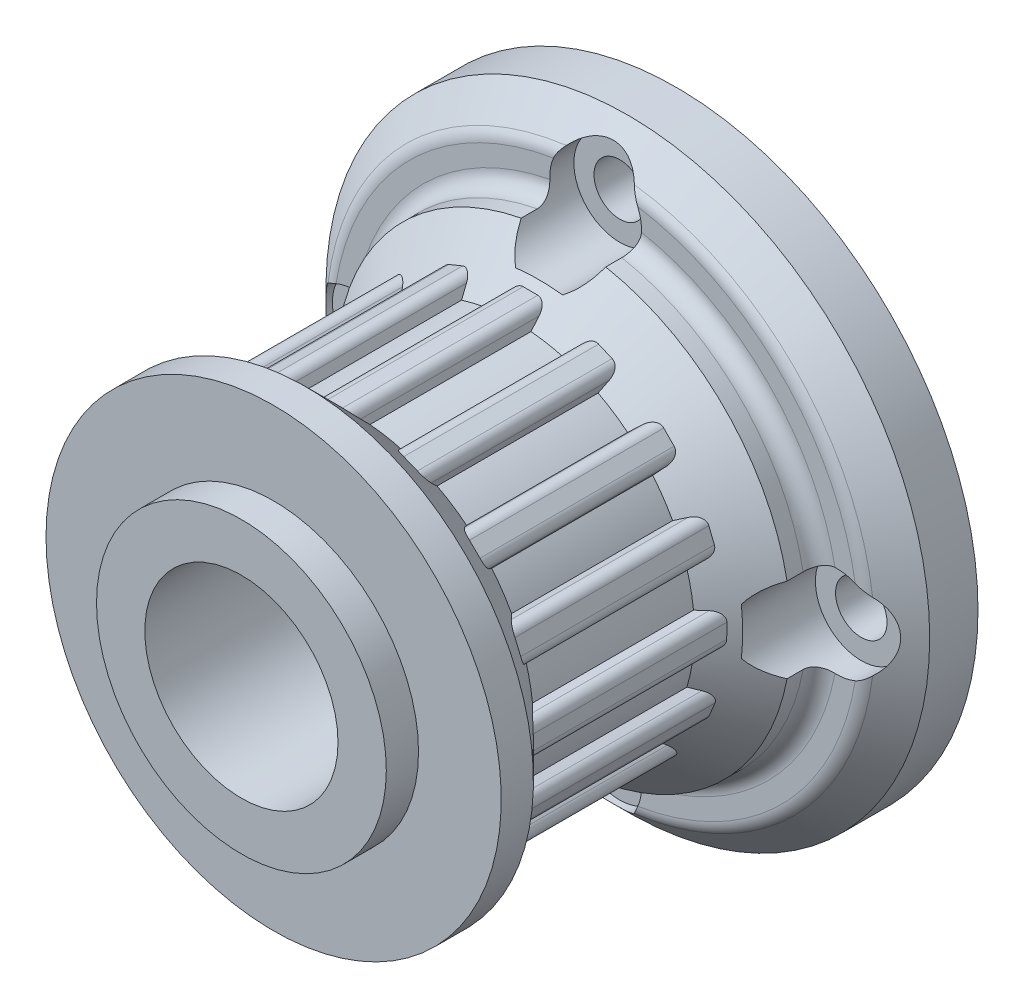
SolidWorks part; units mm, degrees
material "ABS"
ref_plane "Plan de face" through (0, 0, 0) normal (0, 0, 1) x (1, 0, 0)
ref_plane "Plan de dessus" through (0, 0, 0) normal (0, 1, 0) x (1, 0, 0)
ref_plane "Plan de droite" through (0, 0, 0) normal (1, 0, 0) x (0, 0, -1)
sketch "Esquisse5" plane through (0, 0, 0) normal (0, 0, 1) x (1, 0, 0)
  line L0 (0, 0) -> (0, 12.73) construction
  line L1 (0, 0) -> (4.8716, 11.761) construction
  line L2 (0, 12.1967) -> (0.3458, 12.1967)
  line L3 (0.9441, 11.6417) -> (0.9973, 10.9349)
  line L4 (0.9973, 10.9349) -> (3.0608, 10.5451)
  line L5 (3.0608, 10.5451) -> (3.3634, 11.174)
  line L6 (4.1337, 11.4681) -> (4.6599, 11.2501)
  line L7 (0, 0) -> (2.029, 10.74) construction
  line L8 (4.6599, 11.2501) -> (4.9794, 11.1178)
  line L9 (5.3198, 10.3761) -> (5.0985, 9.7028)
  line L10 (5.0985, 9.7028) -> (6.8557, 8.553)
  line L11 (6.8557, 8.553) -> (7.3759, 9.0181)
  line L12 (8.2001, 8.9951) -> (8.6029, 8.5923)
  line L13 (8.6029, 8.5923) -> (8.8475, 8.3478)
  line L14 (8.8781, 7.5323) -> (8.4159, 6.995)
  line L15 (8.4159, 6.995) -> (9.5994, 5.2602)
  line L16 (9.5994, 5.2602) -> (10.2581, 5.4909)
  line L17 (11.0107, 5.1542) -> (11.2287, 4.6279)
  line L18 (11.2287, 4.6279) -> (11.361, 4.3084)
  line L19 (11.0772, 3.5433) -> (10.4447, 3.2237)
  line L20 (10.4447, 3.2237) -> (10.8742, 1.1681)
  line L21 (10.8742, 1.1681) -> (11.571, 1.1292)
  line L22 (12.1375, 0.5301) -> (12.1375, -0.0395)
  line L23 (12.1375, -0.0395) -> (12.1375, -0.3853)
  line L24 (11.5825, -0.9837) -> (10.8758, -1.0368)
  line L25 (10.8758, -1.0368) -> (10.4859, -3.1003)
  line L26 (10.4859, -3.1003) -> (11.1148, -3.4029)
  line L27 (11.4089, -4.1732) -> (11.1909, -4.6995)
  line L28 (11.1909, -4.6995) -> (11.0586, -5.019)
  line L29 (10.3169, -5.3593) -> (9.6436, -5.138)
  line L30 (9.6436, -5.138) -> (8.4938, -6.8952)
  line L31 (8.4938, -6.8952) -> (8.9589, -7.4155)
  line L32 (8.9359, -8.2397) -> (8.5331, -8.6425)
  line L33 (8.5331, -8.6425) -> (8.2886, -8.887)
  line L34 (7.4731, -8.9176) -> (6.9358, -8.4555)
  line L35 (6.9358, -8.4555) -> (5.201, -9.6389)
  line L36 (5.201, -9.6389) -> (5.4317, -10.2976)
  line L37 (5.095, -11.0503) -> (4.5687, -11.2682)
  line L38 (4.5687, -11.2682) -> (4.2493, -11.4006)
  line L39 (3.4841, -11.1168) -> (3.1645, -10.4842)
  line L40 (3.1645, -10.4842) -> (1.1089, -10.9137)
  line L41 (1.1089, -10.9137) -> (1.07, -11.6105)
  line L42 (0.4709, -12.177) -> (-0.0987, -12.177)
  line L43 (-0.0987, -12.177) -> (-0.4445, -12.177)
  line L44 (-1.0428, -11.622) -> (-1.096, -10.9153)
  line L45 (-1.096, -10.9153) -> (-3.1595, -10.5255)
  line L46 (-3.1595, -10.5255) -> (-3.4621, -11.1543)
  line L47 (-4.2324, -11.4485) -> (-4.7587, -11.2305)
  line L48 (-4.7587, -11.2305) -> (-5.0781, -11.0981)
  line L49 (-5.4185, -10.3564) -> (-5.1972, -9.6831)
  line L50 (-5.1972, -9.6831) -> (-6.9544, -8.5333)
  line L51 (-6.9544, -8.5333) -> (-7.4747, -8.9985)
  line L52 (-8.2989, -8.9755) -> (-8.7017, -8.5727)
  line L53 (-8.7017, -8.5727) -> (-8.9462, -8.3282)
  line L54 (-8.9768, -7.5127) -> (-8.5147, -6.9753)
  line L55 (-8.5147, -6.9753) -> (-9.6981, -5.2406)
  line L56 (-9.6981, -5.2406) -> (-10.3568, -5.4712)
  line L57 (-11.1094, -5.1346) -> (-11.3274, -4.6083)
  line L58 (-11.3274, -4.6083) -> (-11.4598, -4.2888)
  line L59 (-11.176, -3.5237) -> (-10.5434, -3.2041)
  line L60 (-10.5434, -3.2041) -> (-10.9729, -1.1485)
  line L61 (-10.9729, -1.1485) -> (-11.6697, -1.1095)
  line L62 (-12.2362, -0.5105) -> (-12.2362, 0.0592)
  line L63 (-12.2362, 0.0592) -> (-12.2362, 0.405)
  line L64 (-11.6812, 1.0033) -> (-10.9745, 1.0565)
  line L65 (-10.9745, 1.0565) -> (-10.5846, 3.1199)
  line L66 (-10.5846, 3.1199) -> (-11.2135, 3.4226)
  line L67 (-11.5076, 4.1928) -> (-11.2897, 4.7191)
  line L68 (-11.2897, 4.7191) -> (-11.1573, 5.0386)
  line L69 (-10.4156, 5.379) -> (-9.7423, 5.1576)
  line L70 (-9.7423, 5.1576) -> (-8.5925, 6.9149)
  line L71 (-8.5925, 6.9149) -> (-9.0577, 7.4351)
  line L72 (-9.0347, 8.2593) -> (-8.6319, 8.6621)
  line L73 (-8.6319, 8.6621) -> (-8.3873, 8.9066)
  line L74 (-7.5718, 8.9373) -> (-7.0345, 8.4751)
  line L75 (-7.0345, 8.4751) -> (-5.2997, 9.6586)
  line L76 (-5.2997, 9.6586) -> (-5.5304, 10.3172)
  line L77 (-5.1938, 11.0699) -> (-4.6675, 11.2879)
  line L78 (-4.6675, 11.2879) -> (-4.348, 11.4202)
  line L79 (-3.5828, 11.1364) -> (-3.2633, 10.5038)
  line L80 (-3.2633, 10.5038) -> (-1.2077, 10.9333)
  line L81 (-1.2077, 10.9333) -> (-1.1687, 11.6301)
  line L82 (-0.5697, 12.1967) -> (0, 12.1967)
  circle A0 centre (0, 0) radius 12.73 construction
  circle A1 centre (0, 0) radius 12.23 construction
  circle A2 centre (0, 0) radius 10.93 construction
  arc A3 (4.1337, 11.4681) -> (3.3634, 11.174) centre (3.904, 10.9138) ccw
  arc A4 (0.9441, 11.6417) -> (0.3458, 12.1967) centre (0.3458, 11.5967) ccw
  arc A5 (8.2001, 8.9951) -> (7.3759, 9.0181) centre (7.7759, 8.5709) ccw
  arc A6 (5.3198, 10.3761) -> (4.9794, 11.1178) centre (4.7498, 10.5634) ccw
  arc A7 (11.0107, 5.1542) -> (10.2581, 5.4909) centre (10.4564, 4.9246) ccw
  arc A8 (8.8781, 7.5323) -> (8.8475, 8.3478) centre (8.4232, 7.9235) ccw
  arc A9 (12.1375, 0.5301) -> (11.571, 1.1292) centre (11.5375, 0.5301) ccw
  arc A10 (11.0772, 3.5433) -> (11.361, 4.3084) centre (10.8067, 4.0788) ccw
  arc A11 (11.4089, -4.1732) -> (11.1148, -3.4029) centre (10.8546, -3.9436) ccw
  arc A12 (11.5825, -0.9837) -> (12.1375, -0.3853) centre (11.5375, -0.3853) ccw
  arc A13 (8.9359, -8.2397) -> (8.9589, -7.4155) centre (8.5117, -7.8154) ccw
  arc A14 (10.3169, -5.3593) -> (11.0586, -5.019) centre (10.5043, -4.7894) ccw
  arc A15 (5.095, -11.0503) -> (5.4317, -10.2976) centre (4.8654, -10.4959) ccw
  arc A16 (7.4731, -8.9176) -> (8.2886, -8.887) centre (7.8644, -8.4627) ccw
  arc A17 (0.4709, -12.177) -> (1.07, -11.6105) centre (0.4709, -11.577) ccw
  arc A18 (3.4841, -11.1168) -> (4.2493, -11.4006) centre (4.0196, -10.8463) ccw
  arc A19 (-4.2324, -11.4485) -> (-3.4621, -11.1543) centre (-4.0028, -10.8941) ccw
  arc A20 (-1.0428, -11.622) -> (-0.4445, -12.177) centre (-0.4445, -11.577) ccw
  arc A21 (-8.2989, -8.9755) -> (-7.4747, -8.9985) centre (-7.8746, -8.5512) ccw
  arc A22 (-5.4185, -10.3564) -> (-5.0781, -11.0981) centre (-4.8485, -10.5438) ccw
  arc A23 (-11.1094, -5.1346) -> (-10.3568, -5.4712) centre (-10.5551, -4.905) ccw
  arc A24 (-8.9768, -7.5127) -> (-8.9462, -8.3282) centre (-8.5219, -7.9039) ccw
  arc A25 (-12.2362, -0.5105) -> (-11.6697, -1.1095) centre (-11.6362, -0.5105) ccw
  arc A26 (-11.176, -3.5237) -> (-11.4598, -4.2888) centre (-10.9054, -4.0592) ccw
  arc A27 (-11.5076, 4.1928) -> (-11.2135, 3.4226) centre (-10.9533, 3.9632) ccw
  arc A28 (-11.6812, 1.0033) -> (-12.2362, 0.405) centre (-11.6362, 0.405) ccw
  arc A29 (-9.0347, 8.2593) -> (-9.0577, 7.4351) centre (-8.6104, 7.8351) ccw
  arc A30 (-10.4156, 5.379) -> (-11.1573, 5.0386) centre (-10.603, 4.809) ccw
  arc A31 (-5.1938, 11.0699) -> (-5.5304, 10.3172) centre (-4.9641, 10.5156) ccw
  arc A32 (-7.5718, 8.9373) -> (-8.3873, 8.9066) centre (-7.9631, 8.4824) ccw
  arc A33 (-0.5697, 12.1967) -> (-1.1687, 11.6301) centre (-0.5697, 11.5967) ccw
  arc A34 (-3.5828, 11.1364) -> (-4.348, 11.4202) centre (-4.1184, 10.8659) ccw
  circle A36 centre (0, 0) radius 6
  point P15 (3.6094, 11.6852)
  point P19 (0.9024, 12.1967)
  point P172 (-0.0494, 0.0098)
  dimension "D1" = 25.46
  dimension "D8" = 0.6
  dimension "D10" = 12
  dimension "D2" = 22.5
  dimension "D3" = 0.5
  dimension "D4" = 1.3
  dimension "D5" = 15
  dimension "D6" = 15
  dimension "D7" = 2.1
  dimension "D9" = 16
sketch "Esquisse11" plane through (0, 0, 0) normal (0, 0, 1) x (1, 0, 0)
  line L0 (0, 15) -> (0, 0) construction
  line L1 (15, 0) -> (0, 0) construction
  line L2 (0, 0) -> (-15, 0) construction
  line L3 (0, 0) -> (0, -15) construction
  circle A1 centre (0, 0) radius 15 construction
  circle A2 centre (0, 0) radius 18.75
  circle A6 centre (-15, 0) radius 1.6
  circle A7 centre (0, 15) radius 1.6
  circle A8 centre (15, 0) radius 1.6
  circle A9 centre (0, -15) radius 1.6
  dimension "D2" = 3.2
  dimension "D3" = 3.2
  dimension "D4" = 3.2
  dimension "D5" = 3.2
  dimension "D6" = 30
  dimension "D1" = 37.5
extrude "Boss.-Extru.4" add sketch "Esquisse11" along normal blind 5
extrude "Boss.-Extru.5" add sketch "Esquisse5" along normal blind 24
sketch "Esquisse12" plane through (0, 0, 5) normal (0, 0, 1) x (1, 0, 0)
  circle A0 centre (0, 0) radius 1.6
  dimension "D1" = 3.2
extrude "Enlèv. mat.-Extru.7" cut sketch "Esquisse12" against normal blind 32
sketch "Esquisse13" plane through (0, 0, 0) normal (0, 1, 0) x (1, 0, 0)
  line L0 (0, 0) -> (0, -25.2892) construction
  line L1 (18.75, 0) -> (-18.75, 0) construction
  line L2 (6, -5) -> (6, -25)
  line L3 (6, -25) -> (14.1375, -25)
  line L4 (14.1375, -25) -> (14.1375, -23)
  line L5 (14.1375, -23) -> (11.1375, -20)
  line L6 (11.1375, -20) -> (11.1375, -10)
  line L7 (11.1375, -10) -> (14.1375, -7)
  line L8 (14.1375, -7) -> (14.1375, -5)
  line L9 (14.1375, -5) -> (6, -5)
  line L10 (12.1375, -24) -> (12.1375, -5) construction
  dimension "D1" = 6
  dimension "D2" = 2
  dimension "D3" = 2
  dimension "D4" = 45
  dimension "D5" = 45
  dimension "D6" = 10
  dimension "D8" = 5
  dimension "D9" = 2
  dimension "D10" = 20
revolve "Révolution1" add sketch "Esquisse13" angle 360 about L0
sketch "Esquisse15" plane through (0, 0, 5) normal (0, 0, 1) x (1, 0, 0)
  circle A8 centre (15, 0) radius 2.85
  circle A9 centre (0, 15) radius 2.85
  circle A10 centre (0, -15) radius 2.85
  circle A11 centre (-15, 0) radius 2.85
extrude "Enlèv. mat.-Extru.9" cut sketch "Esquisse15" against normal blind 1.5 and the other way blind 3.5
chamfer "Chanfrein1" distance 2 angle 45 1 edges at (18.75, 0, 5)
fillet "Congé1" radius 1 8 edges at (9.9967, 9.9967, 5) (-9.9967, 9.9967, 5) (-9.9967, -9.9967, 5) (9.9967, -9.9967, 5) (11.844, 11.844, 5) (11.844, -11.844, 5) (-11.844, -11.844, 5) (-11.844, 11.844, 5)
sketch "Esquisse16" plane through (0, 0, 25) normal (0, 0, 1) x (1, 0, 0)
  circle A0 centre (0, 0) radius 6 construction
  circle A1 centre (0, 0) radius 6
  circle A2 centre (0, 0) radius 9
  dimension "D1" = 18
extrude "Boss.-Extru.6" add sketch "Esquisse16" along normal blind 2
equation "\"A\"= 26"
equation "\"E\"= 20.5"
equation "\"C\"= 6"
equation "\"B\"= 16.5"
equation "\"Dp\"= 25.46'Diamètre primitif"
equation "\"Df\"= 28'Diamètre extérieur"
equation "\"Teeth\"= 16'Nombre de dents"
equation "\"L\"= 15'Largeur courroie"
equation "\"D1\" = \"A\" - \"E\" - 2"
equation "\"D1@Esquisse3\"=\"L\"+2"
equation "\"D2@Esquisse3\"=\"Dp\"/2-5"
equation "\"D1@Esquisse5\"=\"Dp\""
equation "\"D2@Esquisse5\"=360/\"Teeth\""
